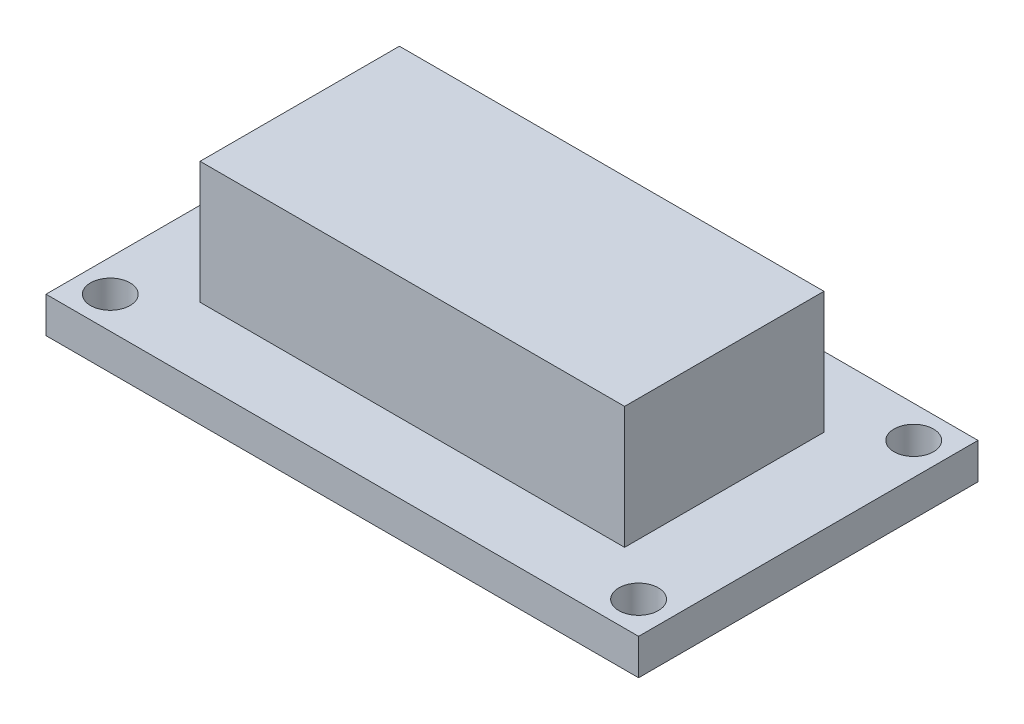
SolidWorks part; units mm, degrees
ref_plane "Front" through (0, 0, 0) normal (0, 0, 1) x (1, 0, 0)
ref_plane "Top" through (0, 0, 0) normal (0, 1, 0) x (1, 0, 0)
ref_plane "Right" through (0, 0, 0) normal (1, 0, 0) x (0, 0, -1)
sketch "Sketch1" plane through (0, 0, 0) normal (0, 1, 0) x (1, 0, 0)
  line L1 (-20.955, 12.0015) -> (20.955, 12.0015)
  line L2 (-20.955, 12.0015) -> (-20.955, -12.0015)
  line L3 (-20.955, -12.0015) -> (20.955, -12.0015)
  line L4 (20.955, 12.0015) -> (20.955, -12.0015)
  line L5 (-20.955, 12.0015) -> (20.955, -12.0015) construction
  line L6 (-20.955, -12.0015) -> (20.955, 12.0015) construction
  line L7 (-55, 0) -> (55, 0) construction
  line L8 (0, -55) -> (0, 55) construction
  circle A0 centre (-18.6817, 9.7282) radius 1.397
  circle A1 centre (-18.6817, -9.7282) radius 1.397
  circle A2 centre (18.6817, -9.7282) radius 1.397
  circle A3 centre (18.6817, 9.7282) radius 1.397
  point P0 (0, 0)
  point P8 (0, 0)
  dimension "D3" = 2.794
  dimension "D1" = 41.91
  dimension "D2" = 24.003
  dimension "D4" = 2.2733
  dimension "D5" = 2.2733
extrude "Boss-Extrude1" add sketch "Sketch1" along normal blind 2.54 contours L2 L3 L4 L1 | A0 | A3 | A2 | A1
sketch "Sketch2" plane through (0, 2.54, 0) normal (0, 1, 0) x (1, 0, 0)
  line L1 (-15.0114, 7.0485) -> (15.0114, 7.0485)
  line L2 (-15.0114, 7.0485) -> (-15.0114, -7.0485)
  line L3 (-15.0114, -7.0485) -> (15.0114, -7.0485)
  line L4 (15.0114, 7.0485) -> (15.0114, -7.0485)
  line L5 (-15.0114, 7.0485) -> (15.0114, -7.0485) construction
  line L6 (-15.0114, -7.0485) -> (15.0114, 7.0485) construction
  point P0 (0, 0)
  dimension "D1" = 30.0228
  dimension "D2" = 14.097
extrude "Boss-Extrude2" add sketch "Sketch2" along normal blind 8.636
